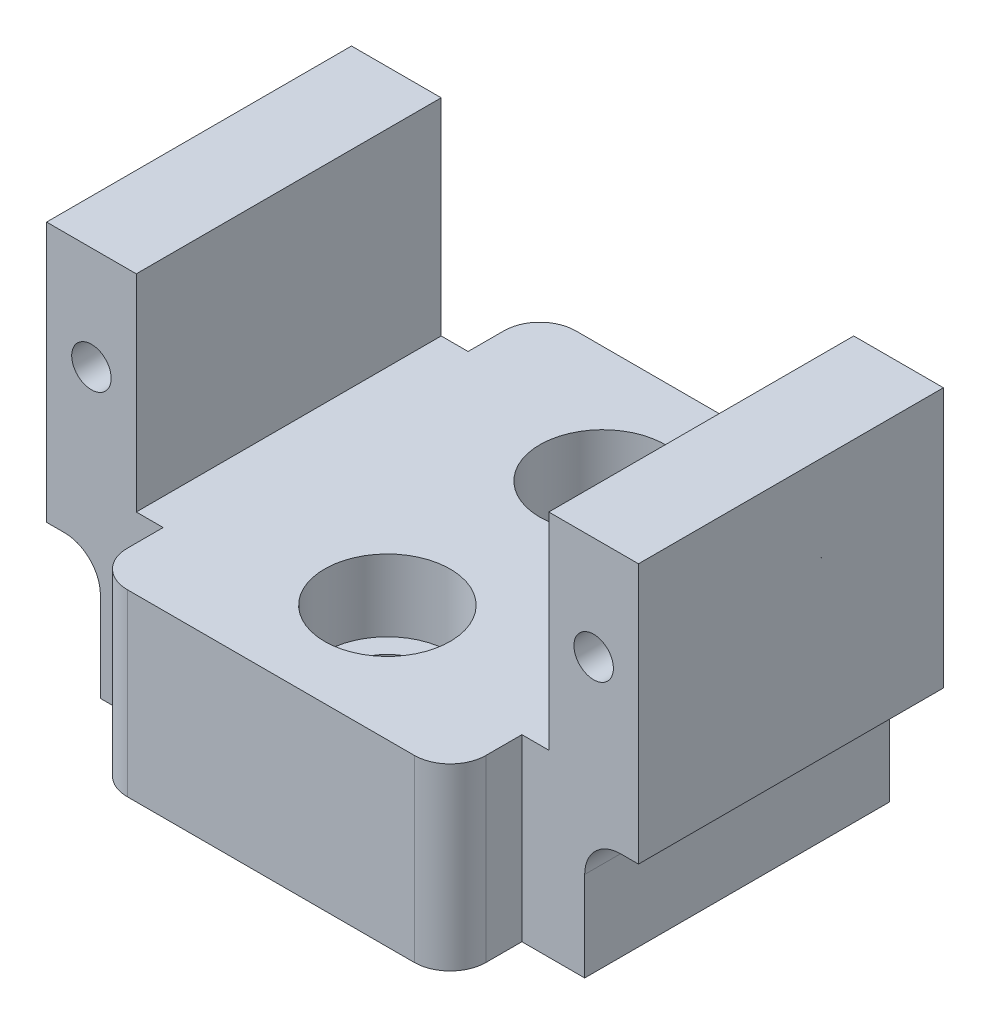
SolidWorks part; units mm, degrees
material "ABS"
ref_plane "Alzado" through (0, 0, 0) normal (0, 0, 1) x (1, 0, 0)
ref_plane "Planta" through (0, 0, 0) normal (0, 1, 0) x (1, 0, 0)
ref_plane "Vista lateral" through (0, 0, 0) normal (1, 0, 0) x (0, 0, -1)
sketch "Croquis2" plane through (0, 0, 0) normal (0, 0, 1) x (1, 0, 0)
  line L2 (0, 0) -> (0, 11.5)
  line L3 (0, 11.5) -> (5, 11.5)
  line L4 (33, 0) -> (33, 11.5)
  line L5 (5, 0) -> (5, 11.5)
  line L6 (28, 0) -> (28, 11.5)
  line L7 (28, 11.5) -> (33, 11.5)
  line L9 (0, 0) -> (0, -3)
  line L10 (0, -3) -> (33, -3)
  line L11 (33, 0) -> (33, -3)
  line L12 (5, 0) -> (28, 0)
  dimension "D1" = 33
  dimension "D2" = 11.5
  dimension "D5" = 5
  dimension "D6" = 5
  dimension "D7" = 3
extrude "Saliente-Extruir1" add sketch "Croquis2" along normal blind 17
sketch "Croquis4" plane through (0, 0, 0) normal (0, 1, 0) x (1, 0, 0)
  line L0 (16.5, -17) -> (16.5, 0) construction
  line L1 (28, -17) -> (5, -17) construction
  line L2 (28, 0) -> (5, 0) construction
  line L3 (9, -8.5) -> (16.5, -8.5) construction
  circle A0 centre (9, -8.5) radius 2.5
  circle A1 centre (24, -8.5) radius 2.5
  dimension "D1" = 5
  dimension "D2" = 7.5
extrude "Cortar-Extruir2" cut sketch "Croquis4" against normal blind 5
sketch "Croquis5" plane through (0, -3, 0) normal (0, -1, 0) x (1, 0, 0)
  line L0 (16.5, 17) -> (16.5, 0) construction
  line L1 (0, 17) -> (33, 17) construction
  line L2 (0, 0) -> (33, 0) construction
  line L4 (3, 0) -> (30, 0)
  line L5 (3, 0) -> (3, 17)
  line L6 (3, 17) -> (30, 17)
  line L7 (30, 0) -> (30, 17)
  line L8 (3, 0) -> (30, 17) construction
  line L9 (3, 17) -> (30, 0) construction
  circle A0 centre (9, 8.5) radius 2.5
  circle A1 centre (24, 8.5) radius 2.5
  point P6 (16.5, 8.5)
  dimension "D1" = 17
  dimension "D2" = 27
extrude "Saliente-Extruir4" add sketch "Croquis5" along normal blind 7
fillet "Redondeo2" radius 2 2 edges at (3, -3, 8.5) (30, -3, 8.5)
sketch "Croquis6" plane through (0, 0, 0) normal (0, 1, 0) x (1, 0, 0)
  circle A0 centre (9, -8.5) radius 3.5
  circle A1 centre (24, -8.5) radius 3.5
  dimension "D1" = 7
  dimension "D2" = 7
extrude "Cortar-Extruir3" cut sketch "Croquis6" against normal blind 1
sketch "Croquis8" plane through (0, 0, 17) normal (0, 0, 1) x (1, 0, 0)
  line L0 (2.5, 5.75) -> (2.5, 11.5) construction
  line L2 (5, 11.5) -> (0, 11.5) construction
  line L3 (2.5, 5.75) -> (0, 5.75) construction
  line L4 (0, 11.5) -> (0, -3) construction
  line L5 (16.5, 0) -> (16.5, 11.5) construction
  line L6 (28, 0) -> (5, 0) construction
  circle A0 centre (2.5, 5.75) radius 1.1
  circle A1 centre (30.5, 5.75) radius 1.1
  dimension "D2" = 2.2
  dimension "D1" = 28
  dimension "D3" = 5.75
sketch "Croquis9" plane through (0, 0, 0) normal (0, 1, 0) x (1, 0, 0)
  circle A0 centre (9, -8.5) radius 3.5
  circle A1 centre (24, -8.5) radius 3.5
extrude "Saliente-Extruir7" add sketch "Croquis9" against normal blind 10
sketch "Croquis10" plane through (0, -10, 0) normal (0, -1, 0) x (1, 0, 0)
  line L0 (16.5, 0) -> (16.5, 17) construction
  line L1 (3, 0) -> (30, 0) construction
  line L2 (30, 17) -> (3, 17) construction
  line L3 (16.5, 2.5) -> (16.5, 14.5) construction
  line L5 (6.5, 21) -> (26.5, 21)
  line L6 (6.5, 21) -> (6.5, -4)
  line L7 (6.5, -4) -> (26.5, -4)
  line L8 (26.5, 21) -> (26.5, -4)
  line L9 (6.5, 21) -> (26.5, -4) construction
  line L10 (6.5, -4) -> (26.5, 21) construction
  circle A0 centre (16.5, 14.5) radius 2.5
  circle A1 centre (16.5, 2.5) radius 2.3
  point P9 (16.5, 8.5)
  point P12 (16.5, 8.5)
  point P13 (16.5, 8.5)
  dimension "D1" = 5
  dimension "D2" = 4.6
  dimension "D3" = 12
  dimension "D4" = 25
  dimension "D5" = 20
extrude "Saliente-Extruir8" add sketch "Croquis10" against normal blind 10 contours L5 L8 L7 L6
sketch "Croquis11" plane through (0, -10, 0) normal (0, -1, 0) x (1, 0, 0)
  line L0 (16.5, 14.5) -> (16.5, 2.5) construction
  line L1 (3, 8.5) -> (30, 8.5) construction
  line L2 (3, 17) -> (3, 0) construction
  line L3 (30, 0) -> (30, 17) construction
  circle A0 centre (16.5, 14.5) radius 2.3
  circle A1 centre (16.5, 2.5) radius 2.3
  point P4 (16.5, 8.5)
  point P11 (16.5, 8.5)
  dimension "D1" = 4.6
  dimension "D2" = 4.6
  dimension "D3" = 12
extrude "Cortar-Extruir6" cut sketch "Croquis11" against normal blind 10
sketch "Croquis12" plane through (0, 0, 0) normal (0, 1, 0) x (1, 0, 0)
  circle A0 centre (16.5, -2.5) radius 3.5
  circle A1 centre (16.5, -14.5) radius 3.5
  dimension "D1" = 7
  dimension "D2" = 7
extrude "Cortar-Extruir7" cut sketch "Croquis12" against normal blind 4
fillet "Redondeo3" radius 2 4 edges at (26.5, -5, -4) (6.5, -5, -4) (6.5, -5, 21) (26.5, -5, 21)
extrude "Cortar-Extruir8" cut sketch "Croquis8" against normal through all
